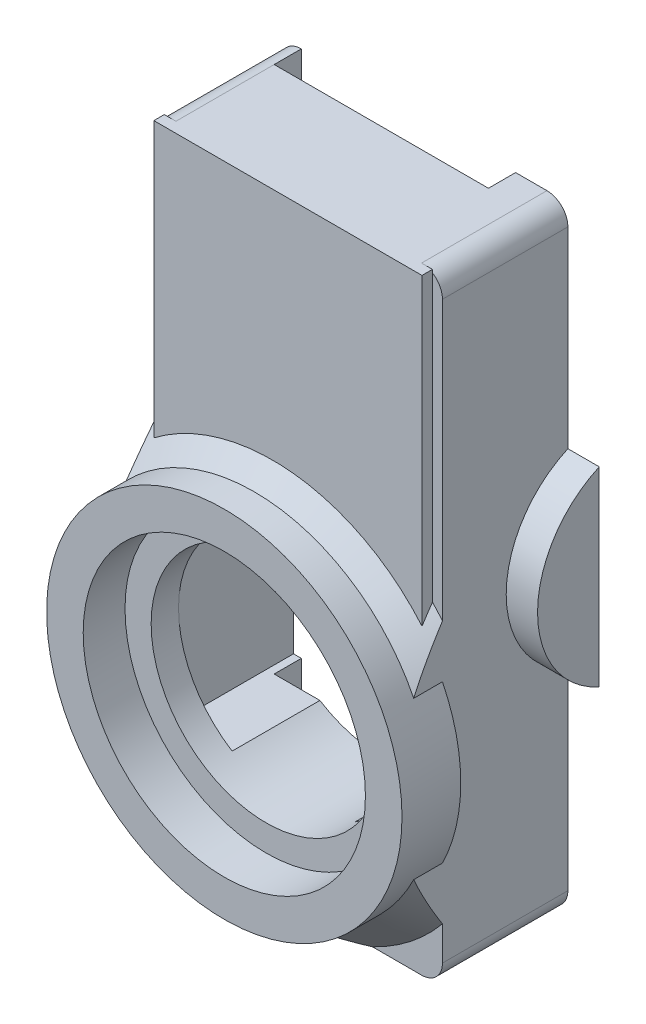
SolidWorks part; units mm, degrees
ref_plane "Front" through (0, 0, 0) normal (0, 0, 1) x (1, 0, 0)
ref_plane "Top" through (0, 0, 0) normal (0, 1, 0) x (1, 0, 0)
ref_plane "Right" through (0, 0, 0) normal (1, 0, 0) x (0, 0, -1)
sketch "Sketch1" plane through (0, 0, 0) normal (0, 0, 1) x (1, 0, 0)
  line L0 (10.25, 22.5) -> (7, 22.5)
  line L1 (7, 22.5) -> (7, 24.7)
  line L2 (3, 24.7) -> (3, 22.5)
  line L3 (3, 22.5) -> (-3, 22.5)
  line L4 (-10.25, -22.5) -> (10.25, -22.5)
  line L5 (10.25, -22.5) -> (10.25, 22.5)
  line L6 (10.25, 22.5) -> (-10.25, 22.5)
  line L7 (-10.25, 22.5) -> (-10.25, -22.5)
  line L12 (-10.25, -22.5) -> (10.25, -22.5) construction
  line L13 (10.25, -22.5) -> (10.25, 22.5)
  line L14 (10.25, 22.5) -> (-10.25, 22.5) construction
  line L15 (-10.25, 22.5) -> (-10.25, -22.5)
  line L16 (15.25, 29.5) -> (-12.25, 29.5)
  line L17 (-12.25, 29.5) -> (-12.25, -29.5)
  line L18 (-12.25, -29.5) -> (15.25, -29.5)
  line L19 (15.25, -29.5) -> (15.25, 29.5)
  line L20 (15.25, 29.5) -> (-12.25, 29.5) construction
  line L21 (-12.25, 29.5) -> (-12.25, -29.5) construction
  line L22 (-12.25, -29.5) -> (15.25, -29.5) construction
  line L23 (15.25, -29.5) -> (15.25, 29.5) construction
  line L24 (15.25, -27.5) -> (15.25, -9.1209)
  line L25 (13.25, 29.5) -> (-12.25, 29.5)
  line L27 (13.25, 29.5) -> (-12.25, 29.5)
  line L32 (-3, 22.5) -> (-3, 24.7)
  line L33 (-7, 24.7) -> (-7, 22.5)
  line L34 (-7, 22.5) -> (-10.25, 22.5)
  line L35 (10.25, -22.5) -> (7, -22.5)
  line L36 (7, -22.5) -> (7, -24.7)
  line L37 (3, -24.7) -> (3, -22.5)
  line L38 (3, -22.5) -> (-3, -22.5)
  line L39 (-3, -22.5) -> (-3, -24.7)
  line L40 (-7, -24.7) -> (-7, -22.5)
  line L41 (-7, -22.5) -> (-10.25, -22.5)
  line L58 (-12.25, 27.5) -> (-12.25, 0)
  line L61 (15.25, -9.1209) -> (15.25, 9.1209)
  line L62 (-12.25, 27.5) -> (-12.25, 0)
  line L63 (-12.25, 0) -> (-12.25, -27.5)
  line L64 (-12.25, 0) -> (-12.25, -27.5)
  line L73 (15.25, -27.5) -> (15.25, -9.1209)
  line L74 (15.25, -9.1209) -> (18.25, -9.1209)
  line L75 (15.25, -9.1209) -> (18.25, -9.1209) construction
  line L76 (18.25, -9.1209) -> (18.25, 9.1209)
  line L77 (18.25, -9.1209) -> (18.25, 9.1209) construction
  line L78 (18.25, 9.1209) -> (15.25, 9.1209)
  line L79 (18.25, 9.1209) -> (15.25, 9.1209) construction
  line L80 (15.25, 9.1209) -> (15.25, 27.5)
  line L81 (15.25, 9.1209) -> (15.25, 27.5)
  line L107 (-12.25, -29.5) -> (13.25, -29.5)
  line L109 (-12.25, -29.5) -> (13.25, -29.5)
  line L113 (-12.25, 0.3464) -> (-12.25, -0.3464)
  circle A1 centre (-5, 24.7) radius 2 construction
  circle A2 centre (5, 24.7) radius 2 construction
  circle A3 centre (5, -24.7) radius 2 construction
  arc A4 (2.909, -23.8692) -> (7.091, -23.8692) centre (5, -24.7) ccw construction
  arc A5 (-7.091, -23.8692) -> (-2.909, -23.8692) centre (-5, -24.7) ccw construction
  arc A6 (-2.909, 23.8692) -> (-7.091, 23.8692) centre (-5, 24.7) ccw construction
  arc A7 (7.091, 23.8692) -> (2.909, 23.8692) centre (5, 24.7) ccw construction
  circle A16 centre (-5, -24.7) radius 2 construction
  arc A21 (7, 24.7) -> (3, 24.7) centre (5, 24.7) ccw
  arc A22 (-3, 24.7) -> (-7, 24.7) centre (-5, 24.7) ccw
  arc A23 (7, -24.7) -> (3, -24.7) centre (5, -24.7) cw
  arc A24 (-3, -24.7) -> (-7, -24.7) centre (-5, -24.7) cw
  arc A28 (-10.25, 29.5) -> (-12.25, 27.5) centre (-10.25, 27.5) ccw
  arc A29 (-10.25, 29.5) -> (-12.25, 27.5) centre (-10.25, 27.5) ccw
  arc A30 (-12.25, -27.5) -> (-10.25, -29.5) centre (-10.25, -27.5) ccw
  arc A31 (-12.25, -27.5) -> (-10.25, -29.5) centre (-10.25, -27.5) ccw
  arc A32 (13.25, -29.5) -> (15.25, -27.5) centre (13.25, -27.5) ccw
  arc A33 (13.25, -29.5) -> (15.25, -27.5) centre (13.25, -27.5) ccw
  arc A34 (15.25, 27.5) -> (13.25, 29.5) centre (13.25, 27.5) ccw
  arc A35 (15.25, 27.5) -> (13.25, 29.5) centre (13.25, 27.5) ccw
  dimension "D4" = 4
  dimension "D1" = 0
  dimension "D2" = 0
  dimension "D3" = 0
extrude "Boss-Extrude1" add sketch "Sketch1" along normal up to surface (11 mm away) contours L109 L27 A16 L12 L15 L14 A1 A2 L13 A3 region at (14.2039, 28.4539, 0)
ref_plane "Plane1" through (0, 0, 12) normal (0, 0, 1) x (1, 0, 0)
sketch "Sketch2" plane through (0, 29.5, 0) normal (0, 1, 0) x (1, 0, 0)
  line L0 (13.25, 0) -> (-10.25, 0) construction
  line L1 (10.25, -2.6) -> (-10.25, -2.6)
  line L2 (10.25, -2.6) -> (10.25, 0)
  line L3 (10.25, 0) -> (-10.25, 0)
  line L4 (-10.25, -2.6) -> (-10.25, 0)
  line L8 (10.25, -11) -> (10.25, 0) construction
  line L9 (-10.25, -11) -> (-10.25, 0) construction
  dimension "D1" = 2.6
extrude "Cut-Extrude1" cut sketch "Sketch2" against normal through all both and the other way through all
sketch "Sketch3" plane through (0, 0, 11) normal (0, 0, 1) x (1, 0, 0)
  line L4 (-10.25, -29.5) -> (13.25, -29.5)
  line L7 (-10.25, -29.5) -> (13.25, -29.5)
  line L14 (13.25, 29.5) -> (-10.25, 29.5)
  line L16 (-12.25, 27.5) -> (-12.25, -27.5)
  line L19 (-12.25, 27.5) -> (-12.25, -27.5)
  line L25 (15.25, -27.5) -> (15.25, 27.5)
  line L27 (15.25, -27.5) -> (15.25, 27.5)
  line L28 (13.25, 29.5) -> (-10.25, 29.5)
  arc A4 (13.25, -29.5) -> (15.25, -27.5) centre (13.25, -27.5) ccw
  arc A5 (13.25, -29.5) -> (15.25, -27.5) centre (13.25, -27.5) ccw
  arc A6 (15.25, 27.5) -> (13.25, 29.5) centre (13.25, 27.5) ccw
  arc A7 (15.25, 27.5) -> (13.25, 29.5) centre (13.25, 27.5) ccw
  arc A8 (-10.25, 29.5) -> (-12.25, 27.5) centre (-10.25, 27.5) ccw
  arc A9 (-10.25, 29.5) -> (-12.25, 27.5) centre (-10.25, 27.5) ccw
  arc A10 (-12.25, -27.5) -> (-10.25, -29.5) centre (-10.25, -27.5) ccw
  arc A11 (-12.25, -27.5) -> (-10.25, -29.5) centre (-10.25, -27.5) ccw
  dimension "D1" = 0
extrude "Boss-Extrude3" add sketch "Sketch3" along normal blind 1 and the other way up to surface (8.4 mm away) other way up to face at (0, -24.7333, 2.6)
sketch "Sketch4" plane through (0, 0, 17.62) normal (0, 0, 1) x (1, 0, 0)
  circle A0 centre (0, -11.7) radius 1.2645 construction
  circle A1 centre (0, -11.7) radius 10
  circle A2 centre (0, -11.7) radius 17
  dimension "D2" = 20
  dimension "D1" = 34
extrude "Boss-Extrude2" add sketch "Sketch4" against normal up to surface (5.62 mm away) up to face at (1.5, 0, 12)
sketch "Sketch5" plane through (0, 0, 17.62) normal (0, 0, 1) x (1, 0, 0)
  circle A0 centre (0, -11.7) radius 13.5
  circle A2 centre (0, -11.7) radius 10 construction
  dimension "D1" = 27
extrude "Cut-Extrude2" cut sketch "Sketch5" against normal blind 4
sketch "Sketch6" plane through (0, 0, 13.62) normal (0, 0, 1) x (1, 0, 0)
  circle A0 centre (0, -11.7) radius 10.5
  dimension "D1" = 21
extrude "Cut-Extrude3" cut sketch "Sketch6" against normal through all both and the other way through all
sketch "Sketch18" plane through (0, 0, 12) normal (0, 0, 1) x (1, 0, 0)
  circle A0 centre (0, -11.7) radius 17
  circle A2 centre (0, -11.7) radius 13.5 construction
  circle A3 centre (0, -11.7) radius 17 construction
extrude "Boss-Extrude4" add sketch "Sketch18" along normal offset from surface (1.12 mm away) 4.5 up to face at (13.5, -11.7, 17.62)
chamfer "Chamfer3" distance 2.75 angle 45 2 edges at (2.6112, -28.4983, 12) (2.6112, 5.0983, 12)
sketch "Sketch19" plane through (0, 0, 12) normal (0, 0, 1) x (1, 0, 0)
  line L33 (-11.3604, 0.9468) -> (-11.3604, 29.5)
  line L36 (-11.3604, 29.5) -> (14.2944, 29.5)
  line L37 (14.2944, 29.5) -> (14.2944, -2.4983)
  arc A7 (-11.3604, 0.9468) -> (14.2944, -2.4983) centre (0, -11.7) cw
  circle A8 centre (0, -11.7) radius 17 construction
extrude "Boss-Extrude7" add sketch "Sketch19" along normal offset from surface (1 mm away) 1 contours A7 region at (1.6974, 16.3862, 12) up to face at (1.6002, 20.8479, 12) offset beyond the face yes
sketch "Sketch28" plane through (0, 0, 12) normal (0, 0, -1) x (-1, 0, 0)
  line L0 (-5.5, 24) -> (5.5, 24) construction
  line L2 (-5.5, -24) -> (5.5, -24) construction
  line L3 (0, -24) -> (0, 24) construction
  line L5 (-11, -21) -> (11, -21)
  line L6 (-11, -21) -> (-11, 21)
  line L7 (-11, 21) -> (11, 21)
  line L8 (11, -21) -> (11, 21)
  line L9 (-11, -21) -> (11, 21) construction
  line L10 (-11, 21) -> (11, -21) construction
  point P11 (0, 0)
  dimension "D1" = 22
  dimension "D2" = 42
extrude "Cut-Extrude17" cut sketch "Sketch28" against normal blind 11 from surface starting at face at (12.3848, -2.925, 0)
sketch "Sketch29" plane through (0, 0, 13.12) normal (0, 0, 1) x (1, 0, 0)
  circle A1 centre (0, -11.7) radius 13.5 construction
  circle A5 centre (0, -11.7) radius 11
  dimension "D1" = 22
extrude "Cut-Extrude18" cut sketch "Sketch29" against normal through all both and the other way through all
sketch "Sketch31" plane through (0, 0, 2.6) normal (0, 0, -1) x (-1, 0, 0)
  circle A0 centre (5, 24.7) radius 1.9
  circle A1 centre (-5, 24.7) radius 1.9
  circle A2 centre (-5, -24.7) radius 1.9
  circle A3 centre (5, -24.7) radius 1.9
  dimension "D1" = 3.8
extrude "Cut-Extrude19" cut sketch "Sketch31" against normal blind 7
ref_plane "Plane2" through (18.25, 9.1209, 0) normal (0, -0.41, 0.9121) x (1, 0, 0)
sketch "Sketch35" plane through (15.25, 0, 0) normal (1, 0, 0) x (0, 0, -1)
  line L0 (-2.7591, 15.2587) -> (2.7591, 2.9831) construction
  line L1 (0, -9.1209) -> (0, 9.1209)
  circle A1 centre (4.1, 0) radius 10 construction
  arc A2 (0, -9.1209) -> (0, 9.1209) centre (4.1, 0) ccw construction
  arc A3 (0, -9.1209) -> (0, 9.1209) centre (4.1, 0) cw
extrude "Boss-Extrude8" add sketch "Sketch35" along normal up to surface (3 mm away)
